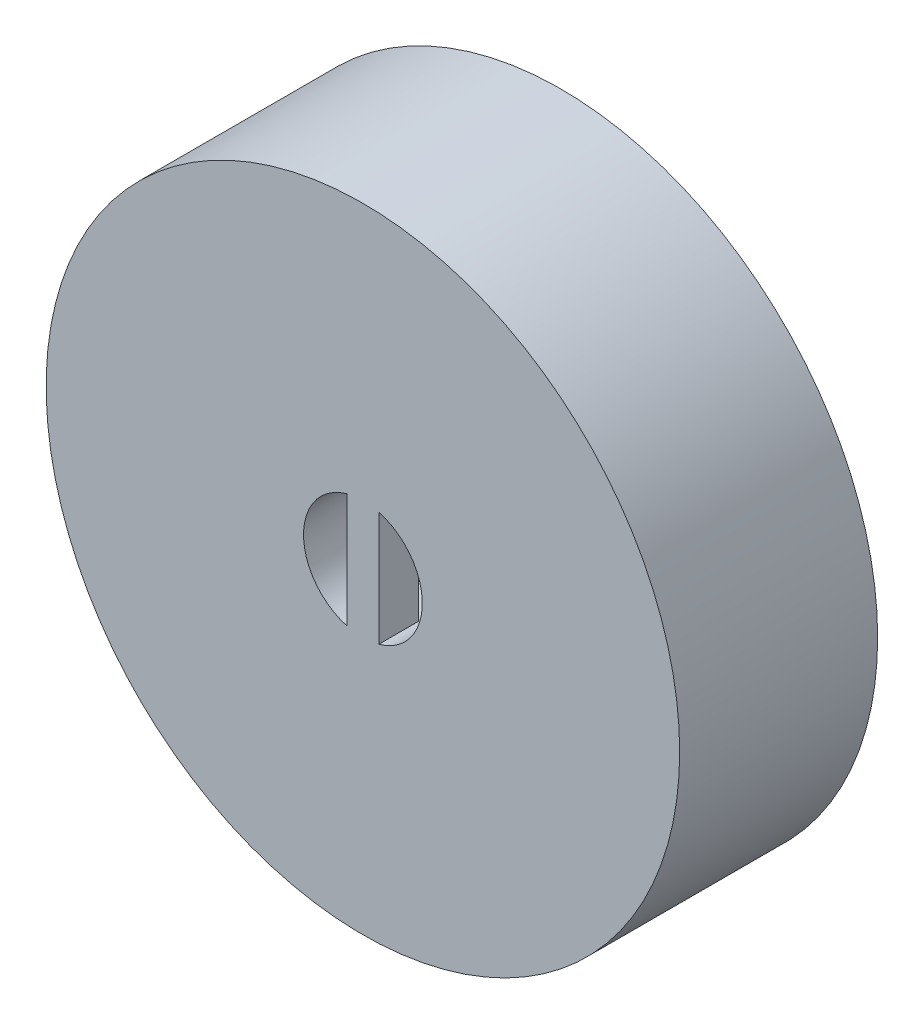
SolidWorks part; units mm, degrees
material "Plain Carbon Steel"
ref_plane "Front Plane" through (0, 0, 0) normal (0, 0, 1) x (1, 0, 0)
ref_plane "Top Plane" through (0, 0, 0) normal (0, 1, 0) x (1, 0, 0)
ref_plane "Right Plane" through (0, 0, 0) normal (1, 0, 0) x (0, 0, -1)
sketch "Sketch1" plane through (0, 0, 0) normal (0, 0, 1) x (1, 0, 0)
  circle A0 centre (0, 0) radius 25.4
  circle A1 centre (0, 0) radius 4.7625
  circle A2 centre (0, 0) radius 9.525
  dimension "D1" = 50.8
  dimension "D2" = 9.525
  dimension "D3" = 19.05
extrude "Boss-Extrude1" add sketch "Sketch1" along normal blind 15.875 contours A0 A2 | A2 A1 region at (-24.6816, 0, 0) region at (-9.2556, 0, 0)
extrude "Boss-Extrude2" add sketch "Sketch1<3>" against normal blind 9.525 contours A2 A1 region at (-9.2556, 0, 0)
sketch "Sketch1<3>" plane through (0, 0, 0) normal (0, 0, 1) x (1, 0, 0) same geometry as "Sketch1"
fillet "Fillet1" radius 2.54 1 edges at (9.525, 0, 0)
sketch "Sketch2" plane through (0, 0, 15.875) normal (0, 0, 1) x (1, 0, 0)
  line L0 (0, 0) -> (0, 50000) construction
  line L1 (-1.27, 4.59) -> (-1.27, -4.59)
  line L2 (1.27, 4.59) -> (1.27, -4.59)
  circle A0 centre (0, 0) radius 4.7625 construction
  arc A1 (-1.27, -4.59) -> (1.27, -4.59) centre (0, 0) ccw
  arc A2 (1.27, 4.59) -> (-1.27, 4.59) centre (0, 0) ccw
  dimension "D1" = 2.54
extrude "Boss-Extrude3" add sketch "Sketch2" against normal blind 3.175
